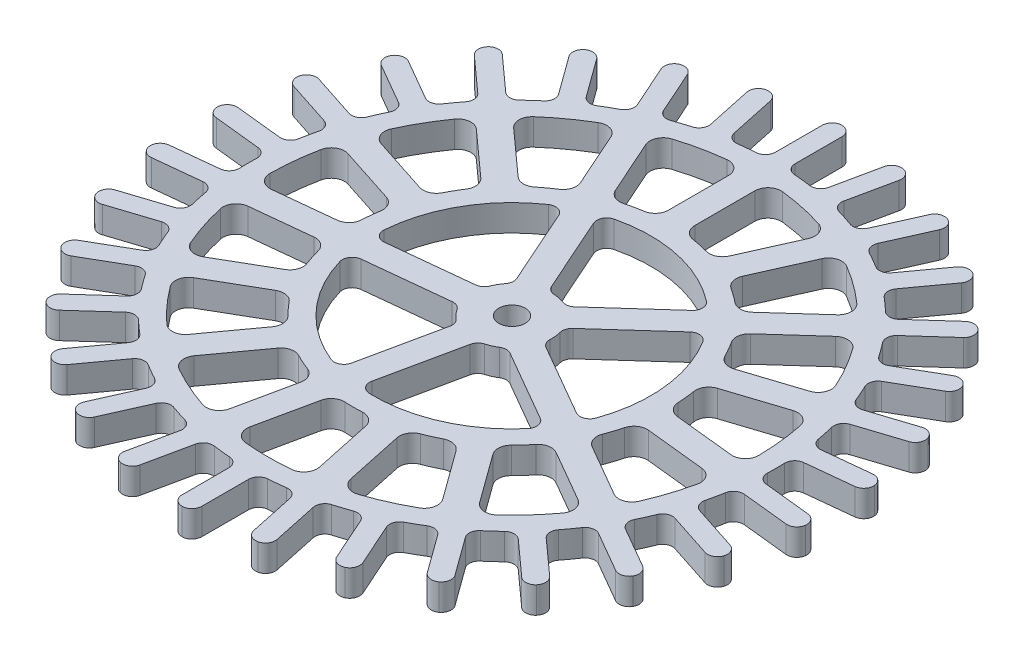
SolidWorks part; units mm, degrees
ref_plane "Front Plane" through (0, 0, 0) normal (0, 0, 1) x (1, 0, 0)
ref_plane "Top Plane" through (0, 0, 0) normal (0, 1, 0) x (1, 0, 0)
ref_plane "Right Plane" through (0, 0, 0) normal (1, 0, 0) x (0, 0, -1)
sketch "Sketch1" plane through (0, 0, 0) normal (0, 1, 0) x (1, 0, 0)
  circle A0 centre (0, 0) radius 127
  dimension "D1" = 254
extrude "Boss-Extrude1" add sketch "Sketch1" along normal blind 12.7
sketch "Sketch2" plane through (0, 12.7, 0) normal (0, 1, 0) x (1, 0, 0)
  line L0 (0, 158.6607) -> (0, 0) construction
  line L1 (-4.7625, 126.9107) -> (4.7625, 126.9107)
  line L2 (-4.7625, 158.6607) -> (4.7625, 158.6607)
  line L3 (4.7625, 158.6607) -> (4.7625, 126.9107)
  line L4 (-4.7625, 158.6607) -> (-4.7625, 126.9107)
  line L8 (-4.7625, 126.9107) -> (4.7625, 126.9107)
  circle A0 centre (0, 0) radius 127 construction
  point P2 (0, 0)
  point P7 (0, 0)
  point P9 (0, 0)
  circle M4 centre (0, 0) radius 127
  dimension "D1" = 31.75
  dimension "D2" = 9.525
extrude "Boss-Extrude2" add sketch "Sketch2" against normal up to surface (12.7 mm away) contours L2 L0 L3 M4 | L0 L2 L4 M4 region at (2.3824, 12.7, -142.8154) region at (-2.3824, 12.7, -142.8154) up to face at (0, 0, 127)
fillet "Fillet1" radius 4.7625 4 edges at (-4.7625, 6.35, -158.6607) (-4.7625, 6.35, -126.9107) (4.7625, 6.35, -126.9107) (4.7625, 6.35, -158.6607)
pattern_circular "CirPattern1" count 30 over 360 about axis through (0, 12.7, 0) along (0, 1, 0) of "Boss-Extrude2", "Fillet1"
sketch "Sketch3" plane through (0, 12.7, 0) normal (0, 1, 0) x (1, 0, 0)
  circle A0 centre (0, 0) radius 6.35
  dimension "D1" = 12.7
extrude "Cut-Extrude1" cut sketch "Sketch3" against normal through all
sketch "Sketch4" plane through (0, 12.7, 0) normal (0, 1, 0) x (1, 0, 0)
  line L0 (41.9105, 109.7446) -> (25.0845, 71.9528)
  line L1 (6.35, 117.3033) -> (6.35, 75.935)
  line L2 (0, 0) -> (0, 201.1843) construction
  line L3 (0, 0) -> (83.784, 188.182) construction
  arc A0 (6.35, 75.935) -> (25.0845, 71.9528) centre (0, 0) cw
  arc A1 (6.35, 117.3033) -> (41.9105, 109.7446) centre (0, 0) cw
  circle A3 centre (0, 0) radius 127 construction
  dimension "D1" = 24
  dimension "D4" = 9.525
  dimension "D5" = 76.2
  dimension "D2" = 12.7
  dimension "D3" = 12.7
extrude "Cut-Extrude2" cut sketch "Sketch4" against normal through all contours A1 L0 A0 L1
fillet "Fillet2" radius 6.35 4 edges at (6.35, 6.35, -75.935) (25.0845, 6.35, -71.9528) (41.9105, 6.35, -109.7446) (6.35, 6.35, -117.3033)
pattern_circular "CirPattern3" count 15 over 360 about axis through (0, 0, 0) along (0, 1, 0) of "Fillet2", "Cut-Extrude2"
sketch "Sketch6" plane through (0, 12.7, 0) normal (0, 1, 0) x (1, 0, 0)
  line L0 (-21.1949, 63.2166) -> (-1.5042, 18.9905)
  line L1 (45.075, 49.1305) -> (9.0983, 16.7369)
  line L2 (0, 0) -> (79.6649, 71.7306) construction
  line L3 (86.2899, 69.151) -> (64.8652, 49.8602) construction
  line L4 (0, 0) -> (-48.1643, 108.1788) construction
  line L5 (-39.1015, 103.4354) -> (-27.3754, 77.0981) construction
  line L6 (77.7919, 78.5889) -> (56.3673, 59.2981) construction
  arc A0 (-21.1949, 63.2166) -> (45.075, 49.1305) centre (0, 0) cw
  arc A1 (-1.5042, 18.9905) -> (9.0983, 16.7369) centre (0, 0) cw
  arc A2 (19.9148, 73.5516) -> (11.7231, 75.2928) centre (0, 0) ccw construction
  dimension "D1" = 19.05
  dimension "D2" = 9.525
extrude "Cut-Extrude3" cut sketch "Sketch6" against normal through all
fillet "Fillet3" radius 4.7625 4 edges at (45.075, 6.35, -49.1305) (9.0983, 6.35, -16.7369) (-1.5042, 6.35, -18.9905) (-21.1949, 6.35, -63.2166)
pattern_circular "CirPattern5" count 5 over 360 about axis through (0, 0, 0) along (0, 1, 0) of "Fillet3", "Cut-Extrude3"
sketch "Sketch5" plane through (0, 12.7, 0) normal (0, 1, 0) x (1, 0, 0)
  arc A0 (-25.4435, 64.1023) -> (37.6936, 57.7553) centre (0, 0) cw
